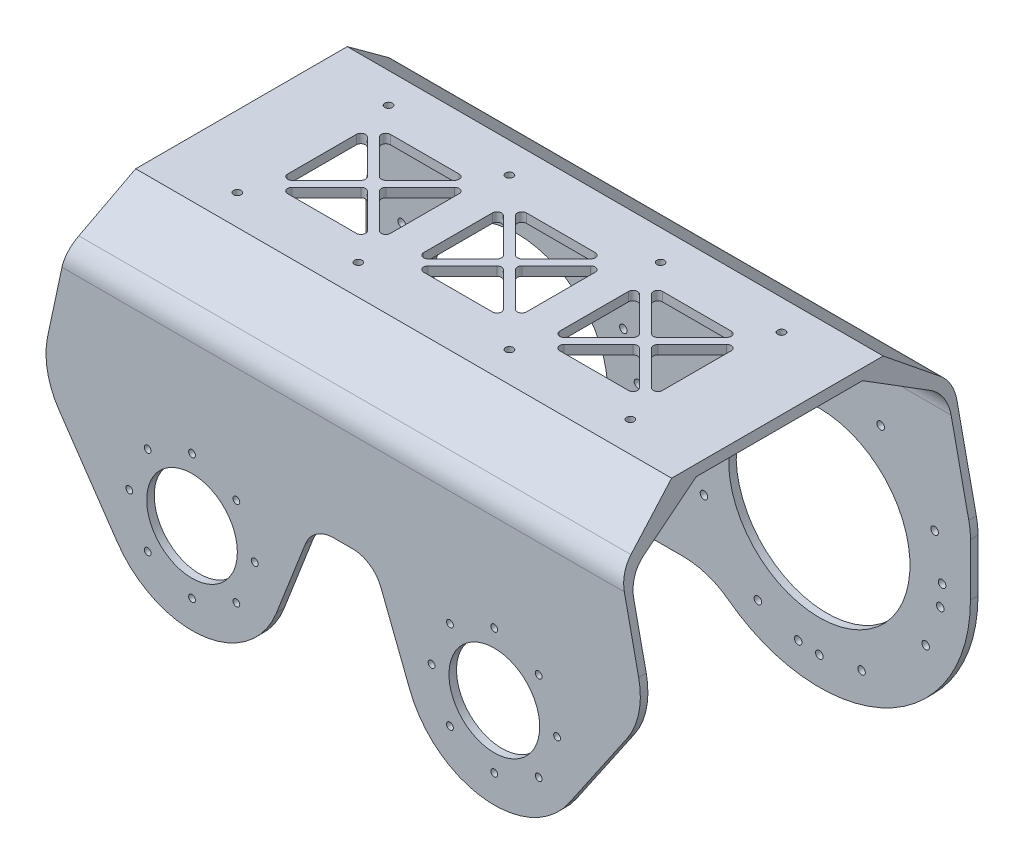
SolidWorks part; units mm, degrees
material "6061 合金"
ref_plane "前视基准面" through (0, 0, 0) normal (0, 0, 1) x (1, 0, 0)
ref_plane "上视基准面" through (0, 0, 0) normal (0, 1, 0) x (1, 0, 0)
ref_plane "右视基准面" through (0, 0, 0) normal (1, 0, 0) x (0, 0, -1)
other "Configuration Table"
sketch "草图1" plane through (0, 0, 0) normal (0, 0, 1) x (1, 0, 0)
  line L0 (0, 350.9244) -> (0, -92.7876) construction
  line L1 (-181.3077, 0) -> (720.1521, 0) construction
  line L5 (200, 120) -> (200, 0)
  line L6 (-200, 120) -> (-200, 0)
  line L8 (-200, 120) -> (-200, 180)
  line L9 (-200, 180) -> (200, 180)
  line L10 (200, 180) -> (200, 120)
  line L11 (-28.5857, -70) -> (28.5857, -70)
  circle A0 centre (100, 0) radius 60
  circle A1 centre (100, 0) radius 85 construction
  arc A2 (28.5857, -70) -> (200, 0) centre (100, 0) ccw
  circle A3 centre (-100, 0) radius 85 construction
  circle A4 centre (-100, 0) radius 60
  arc A5 (-28.5857, -70) -> (-200, 0) centre (-100, 0) cw
  point P16 (0, 176.5389)
  point P17 (0, 80)
  dimension "D1" = 120
  dimension "D2" = 170
  dimension "D4" = 200
  dimension "D3" = 100
  dimension "D5" = 70
  dimension "D9" = 400
  dimension "D10" = 180
extrude "凸台-拉伸1" add sketch "草图1" along normal blind 220
sketch "草图2" plane through (0, 0, 0) normal (1, 0, 0) x (0, 0, -1)
  line L0 (-110, 291.5151) -> (-110, -211.064) construction
  line L1 (0, 0) -> (0, 180) construction
  line L2 (-220, 0) -> (-220, 180) construction
  line L5 (-215, 111.1325) -> (-215, -188.8675)
  line L6 (-215, -188.8675) -> (-5, -188.8675)
  line L7 (-5, 111.1325) -> (-5, -188.8675)
  line L8 (0, -100) -> (0, 0) construction
  line L10 (-215, 111.1325) -> (-165, 140)
  line L11 (-165, 140) -> (-55, 140)
  line L12 (-5, 111.1325) -> (-55, 140)
  line L13 (-220, 180) -> (0, 180) construction
  point P15 (-110, 140)
  dimension "D1" = 5
  dimension "D2" = 40
  dimension "D3" = 300
  dimension "D4" = 30
  dimension "D5" = 110
extrude "切除-拉伸1" cut sketch "草图2" against normal through all both and the other way through all
sketch "草图3" plane through (0, 0, 0) normal (1, 0, 0) x (0, 0, -1)
  line L0 (-110, 274.1056) -> (-110, -160.0053) construction
  line L1 (0, 0) -> (0, 180) construction
  line L2 (-220, 0) -> (-220, 180) construction
  line L3 (-180, 180) -> (-180, 146)
  line L4 (-220, 180) -> (0, 180) construction
  line L5 (-55, 140) -> (-165, 140) construction
  line L6 (-180, 146) -> (-220, 115)
  line L7 (-220, 0) -> (-220, 180) construction
  line L8 (-220, 115) -> (-220, 180)
  line L9 (-220, 180) -> (-180, 180)
  line L10 (0, 180) -> (-40, 180)
  line L11 (0, 115) -> (0, 180)
  line L12 (-40, 146) -> (0, 115)
  line L13 (-40, 180) -> (-40, 146)
  dimension "D1" = 65
  dimension "D2" = 140
  dimension "D3" = 6
extrude "切除-拉伸2" cut sketch "草图3" against normal through all both and the other way through all
sketch "草图4" plane through (0, 0, 0) normal (0, 0, -1) x (-1, 0, 0)
  line L0 (0, 284.6971) -> (0, -204.9481) construction
  line L1 (-100, 0) -> (-72.051, 76.2917) construction
  line L2 (-100, 0) -> (-100, 81.25) construction
  line L3 (-100, 0) -> (-113.9413, 80.045) construction
  line L4 (-100, 0) -> (-140.625, 70.3646) construction
  line L5 (100, 0) -> (140.625, 70.3646) construction
  line L6 (100, 0) -> (113.9413, 80.045) construction
  line L7 (100, 0) -> (100, 81.25) construction
  line L8 (100, 0) -> (72.051, 76.2917) construction
  circle A0 centre (-100, 0) radius 81.25 construction
  circle A1 centre (-72.051, 76.2917) radius 2.5
  circle A2 centre (-100, 81.25) radius 2.5
  circle A3 centre (-113.9413, 80.045) radius 2.5
  circle A4 centre (-140.625, 70.3646) radius 2.5
  circle A5 centre (-23.7083, -27.949) radius 2.5
  circle A6 centre (-18.75, 0) radius 2.5
  circle A7 centre (-19.955, 13.9413) radius 2.5
  circle A8 centre (-29.6354, 40.625) radius 2.5
  circle A9 centre (-127.949, -76.2917) radius 2.5
  circle A10 centre (-100, -81.25) radius 2.5
  circle A11 centre (-86.0587, -80.045) radius 2.5
  circle A12 centre (-59.375, -70.3646) radius 2.5
  circle A13 centre (-176.2917, 27.949) radius 2.5
  circle A14 centre (-181.25, 0) radius 2.5
  circle A15 centre (-180.045, -13.9413) radius 2.5
  circle A16 centre (-170.3646, -40.625) radius 2.5
  circle A17 centre (100, 0) radius 81.25 construction
  circle A18 centre (170.3646, -40.625) radius 2.5
  circle A19 centre (180.045, -13.9413) radius 2.5
  circle A20 centre (181.25, 0) radius 2.5
  circle A21 centre (176.2917, 27.949) radius 2.5
  circle A22 centre (59.375, -70.3646) radius 2.5
  circle A23 centre (86.0587, -80.045) radius 2.5
  circle A24 centre (100, -81.25) radius 2.5
  circle A25 centre (127.949, -76.2917) radius 2.5
  circle A26 centre (29.6354, 40.625) radius 2.5
  circle A27 centre (19.955, 13.9413) radius 2.5
  circle A28 centre (18.75, 0) radius 2.5
  circle A29 centre (23.7083, -27.949) radius 2.5
  circle A30 centre (140.625, 70.3646) radius 2.5
  circle A31 centre (113.9413, 80.045) radius 2.5
  circle A32 centre (100, 81.25) radius 2.5
  circle A33 centre (72.051, 76.2917) radius 2.5
  point P41 (-100, 0)
  point P74 (100, 0)
  dimension "D1" = 162.5
  dimension "D5" = 5
  dimension "D2" = 30
  dimension "D3" = 30
  dimension "D4" = 9.88
  dimension "D6" = 4
extrude "切除-拉伸3" cut sketch "草图4" against normal blind 32.5
sketch "草图5" plane through (0, 0, 220) normal (0, 0, 1) x (1, 0, 0)
  circle A0 centre (-100, 0) radius 60 construction
  circle A1 centre (100, 0) radius 60 construction
  circle A2 centre (-100, 0) radius 60
  circle A3 centre (100, 0) radius 60
  circle A4 centre (100, 0) radius 30
  circle A5 centre (-100, 0) radius 30
  dimension "D1" = 60
extrude "凸台-拉伸2" add sketch "草图5" against normal up to surface (5 mm away) up to face at (160, 0, 215)
sketch "草图6" plane through (0, 0, 220) normal (0, 0, 1) x (1, 0, 0)
  line L0 (0, 0) -> (0, 283.4074) construction
  line L1 (100, 0) -> (100, 76.6247) construction
  line L2 (-100, 0) -> (-100, 76.6247) construction
  circle A0 centre (100, 0) radius 41.5 construction
  circle A1 centre (100, 41.5) radius 2.25
  circle A2 centre (129.3449, 29.3449) radius 2.25
  circle A3 centre (141.5, 0) radius 2.25
  circle A4 centre (129.3449, -29.3449) radius 2.25
  circle A5 centre (100, -41.5) radius 2.25
  circle A6 centre (70.6551, -29.3449) radius 2.25
  circle A7 centre (58.5, 0) radius 2.25
  circle A8 centre (70.6551, 29.3449) radius 2.25
  circle A9 centre (-100, 0) radius 41.5 construction
  circle A10 centre (-70.6551, 29.3449) radius 2.25
  circle A11 centre (-58.5, 0) radius 2.25
  circle A12 centre (-70.6551, -29.3449) radius 2.25
  circle A13 centre (-100, -41.5) radius 2.25
  circle A14 centre (-129.3449, -29.3449) radius 2.25
  circle A15 centre (-141.5, 0) radius 2.25
  circle A16 centre (-129.3449, 29.3449) radius 2.25
  circle A17 centre (-100, 41.5) radius 2.25
  point P26 (100, 0)
  point P44 (-100, 0)
  dimension "D1" = 83
  dimension "D2" = 4.5
  dimension "D3" = 8
extrude "切除-拉伸4" cut sketch "草图6" against normal up to surface (5 mm away) up to face at (0, -5.4819, 215)
sketch "草图7" plane through (0, 0, 220) normal (0, 0, 1) x (1, 0, 0)
  line L0 (0, 0) -> (0, 252.6042) construction
  line L1 (0, 0) -> (0, -112.8952) construction
  line L2 (-20, 40) -> (20, 40)
  line L3 (20, 40) -> (44.1003, -21.7995)
  line L4 (170, 180) -> (200, 180)
  line L5 (-200, 180) -> (200, 180) construction
  line L6 (200, 180) -> (200, 40)
  line L7 (200, 0) -> (200, 115) construction
  line L8 (200, 40) -> (170, 180)
  line L9 (-200, 180) -> (-200, 40)
  line L10 (-170, 180) -> (-200, 180)
  line L11 (-200, 40) -> (-170, 180)
  line L12 (200, 40) -> (149.5399, -33.8497)
  line L13 (-28.5857, -70) -> (28.5857, -70) construction
  line L14 (200, 0) -> (200, 40)
  line L15 (-28.5857, -70) -> (28.5857, -70)
  line L16 (-200, 0) -> (-200, 40)
  line L17 (-200, 40) -> (-149.5399, -33.8497)
  line L18 (-20, 40) -> (-44.1003, -21.7995)
  arc A0 (44.1003, -21.7995) -> (149.5399, -33.8497) centre (100, 0) ccw
  arc A1 (28.5857, -70) -> (200, 0) centre (100, 0) ccw construction
  arc A2 (28.5857, -70) -> (200, 0) centre (100, 0) ccw
  arc A3 (-28.5857, -70) -> (-200, 0) centre (-100, 0) cw
  arc A4 (-44.1003, -21.7995) -> (-149.5399, -33.8497) centre (-100, 0) cw
  point P22 (0, -70)
  point P32 (0, 40)
  line M32 (200, 115) -> (-200, 115)
  line M33 (-200, 115) -> (-200, 0)
  arc M34 (-200, 0) -> (-28.5857, -70) centre (-100, 0) ccw
  line M35 (-28.5857, -70) -> (28.5857, -70)
  arc M36 (28.5857, -70) -> (200, 0) centre (100, 0) ccw
  line M37 (200, 0) -> (200, 115)
  dimension "D1" = 120
  dimension "D2" = 30
  dimension "D3" = 140
  dimension "D4" = 40
  dimension "D5" = 20
extrude "切除-拉伸5" cut sketch "草图7" against normal blind 10 contours L8 L6 L4 M32 | L8 M37 M32 | L18 A4 L17 L12 A0 L3 L2 M33 M34 M35 M36 M37 | L11 L10 L9 M32 | L11 M33 M32 region at (0, -43.351, 220) region at (-194.6429, 90, 220) region at (194.6429, 90, 220) region at (-188.1312, 150.7752, 220) region at (188.1312, 150.7752, 220)
sketch "草图8" plane through (0, 0, 0) normal (0, 0, -1) x (-1, 0, 0)
  line L0 (200, 40) -> (170, 180) construction
  line L1 (200, 180) -> (200, 40) construction
  line L2 (170, 180) -> (200, 180) construction
  line L3 (-200, 40) -> (-170, 180) construction
  line L4 (-200, 180) -> (-200, 40) construction
  line L5 (-170, 180) -> (-200, 180) construction
  line L6 (200, 40) -> (170, 180)
  line L7 (200, 180) -> (200, 40)
  line L8 (170, 180) -> (200, 180)
  line L9 (-200, 40) -> (-170, 180)
  line L10 (-200, 180) -> (-200, 40)
  line L11 (-170, 180) -> (-200, 180)
extrude "切除-拉伸6" cut sketch "草图8" against normal blind 381
fillet "圆角1" radius 50 6 edges at (-200, 40, 217.5) (200, 40, 217.5) (200, 40, 2.5) (28.5857, -70, 2.5) (-28.5857, -70, 2.5) (-200, 40, 2.5)
fillet "圆角2" radius 20 6 edges at (0, 111.1325, 5) (0, 111.1325, 215) (-20, 40, 217.5) (20, 40, 217.5) (0, 115, 0) (0, 115, 220)
sketch "草图9" plane through (0, 0, 220) normal (0, 0, 1) x (1, 0, 0)
  line L1 (-235.8074, 239.4268) -> (177.2857, 239.4268)
  line L2 (-235.8074, 239.4268) -> (-235.8074, 146)
  line L3 (-235.8074, 146) -> (177.2857, 146)
  line L4 (177.2857, 239.4268) -> (177.2857, 146)
extrude "切除-拉伸7" cut sketch "草图9" against normal blind 381
sketch "草图10" plane through (0, 146, 0) normal (0, 1, 0) x (1, 0, 0)
  line L0 (-219.3102, -110) -> (241.5322, -110) construction
  line L1 (0, 0) -> (0, -250.3427) construction
  line L2 (-186.0292, 0) -> (186.0292, 0) construction
  line L3 (-177.2857, -180) -> (177.2857, -180) construction
  line L4 (-177.2857, -40) -> (177.2857, -40) construction
  line L5 (60, -76) -> (120, -76)
  line L6 (120, -76) -> (90, -106)
  line L7 (90, -106) -> (60, -76)
  line L8 (90, 38.8036) -> (90, -139.59) construction
  line L9 (94, -110) -> (124, -80)
  line L10 (124, -80) -> (124, -140)
  line L11 (124, -140) -> (94, -110)
  line L12 (90, -114) -> (120, -144)
  line L13 (120, -144) -> (60, -144)
  line L14 (60, -144) -> (90, -114)
  line L15 (86, -110) -> (56, -140)
  line L16 (56, -140) -> (56, -80)
  line L17 (56, -80) -> (86, -110)
  line L18 (4, -110) -> (34, -80)
  line L19 (34, -80) -> (34, -140)
  line L20 (34, -140) -> (4, -110)
  line L21 (0, -106) -> (-30, -76)
  line L22 (-30, -76) -> (30, -76)
  line L23 (30, -76) -> (0, -106)
  line L24 (-4, -110) -> (-34, -140)
  line L25 (-34, -140) -> (-34, -80)
  line L26 (-34, -80) -> (-4, -110)
  line L27 (0, -114) -> (30, -144)
  line L28 (30, -144) -> (-30, -144)
  line L29 (-30, -144) -> (0, -114)
  line L30 (-86, -110) -> (-56, -80)
  line L31 (-56, -80) -> (-56, -140)
  line L32 (-56, -140) -> (-86, -110)
  line L33 (-90, -106) -> (-120, -76)
  line L34 (-120, -76) -> (-60, -76)
  line L35 (-60, -76) -> (-90, -106)
  line L36 (-94, -110) -> (-124, -140)
  line L37 (-124, -140) -> (-124, -80)
  line L38 (-124, -80) -> (-94, -110)
  line L39 (-90, -114) -> (-60, -144)
  line L40 (-60, -144) -> (-120, -144)
  line L41 (-120, -144) -> (-90, -114)
  circle A0 centre (130, -60) radius 2.5
  circle A1 centre (50, -60) radius 2.5
  circle A4 centre (-50, -60) radius 2.5
  circle A5 centre (-130, -60) radius 2.5
  circle A6 centre (130, -160) radius 2.5
  circle A7 centre (50, -160) radius 2.5
  circle A8 centre (-50, -160) radius 2.5
  circle A9 centre (-130, -160) radius 2.5
  point P34 (90, -110)
  point P44 (90, -110)
  dimension "D1" = 5
  dimension "D2" = 80
  dimension "D3" = 50
  dimension "D4" = 50
  dimension "D5" = 45
  dimension "D6" = 45
  dimension "D7" = 60
  dimension "D8" = 4
  dimension "D9" = 4
  dimension "D11" = 22
  dimension "D10" = 3
extrude "切除-拉伸8" cut sketch "草图10" against normal blind 10
fillet "圆角3" radius 3 36 edges at (-120, 143, 76) (-90, 143, 106) (-60, 143, 76) (-56, 143, 80) (-56, 143, 140) (-86, 143, 110) (-94, 143, 110) (-124, 143, 80) (-124, 143, 140) (-120, 143, 144) (-90, 143, 114) (-60, 143, 144) (30, 143, 76) (0, 143, 106) (-30, 143, 76) (-4, 143, 110) (-34, 143, 80) (-34, 143, 140) (-30, 143, 144) (30, 143, 144) (0, 143, 114) (4, 143, 110) (34, 143, 140) (34, 143, 80) (56, 143, 80) (86, 143, 110) (56, 143, 140) (60, 143, 144) (90, 143, 114) (120, 143, 144) (124, 143, 140) (94, 143, 110) (90, 143, 106) (60, 143, 76) (120, 143, 76) (124, 143, 80)
